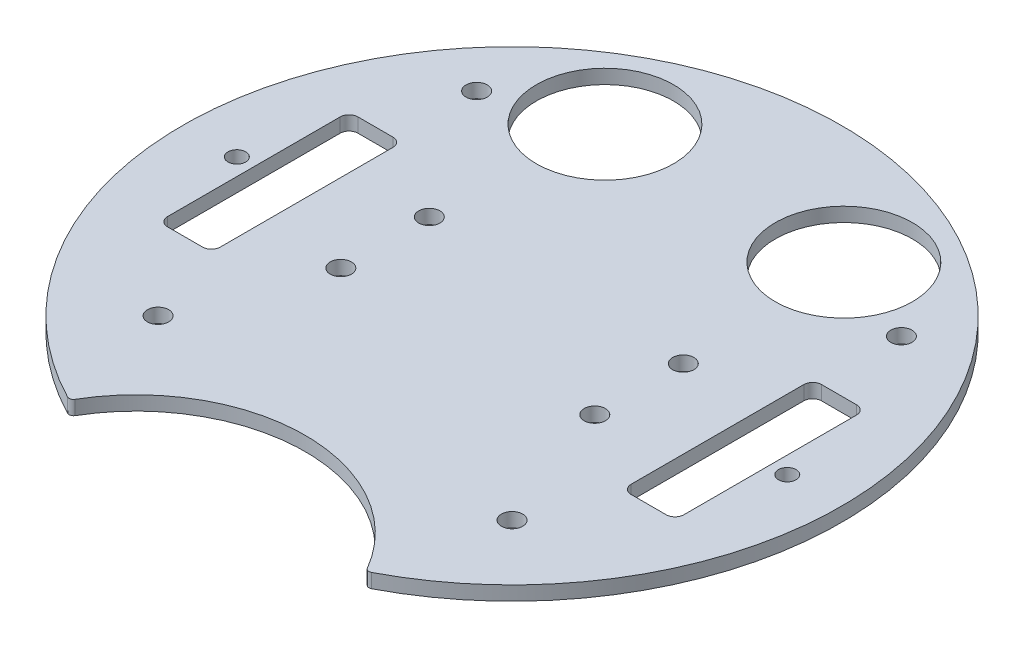
SolidWorks part; units mm, degrees
material "Plain Carbon Steel"
ref_plane "Front Plane" through (0, 0, 0) normal (0, 0, 1) x (1, 0, 0)
ref_plane "Top Plane" through (0, 0, 0) normal (0, 1, 0) x (1, 0, 0)
ref_plane "Right Plane" through (0, 0, 0) normal (1, 0, 0) x (0, 0, -1)
sketch "Sketch1" plane through (0, 0, 0) normal (0, 1, 0) x (1, 0, 0)
  line L1 (0, -85) -> (0, 0) construction
  arc A0 (34.3603, -66.1031) -> (-34.3603, -66.1031) centre (0, 0) ccw
  arc A1 (33.0354, -65.7199) -> (-33.0354, -65.7199) centre (0, -85) ccw
  arc A2 (34.3603, -66.1031) -> (33.0354, -65.7199) centre (33.8991, -65.2158) cw
  arc A3 (-33.0354, -65.7199) -> (-34.3603, -66.1031) centre (-33.8991, -65.2158) cw
  dimension "D1" = 149
  dimension "D2" = 76.5
  dimension "D4" = 1
  dimension "D3" = 85
extrude "Boss-Extrude1" add sketch "Sketch1" along normal blind 3.2
sketch "solenoid placement" plane through (0, 3.2, 0) normal (0, 1, 0) x (1, 0, 0)
  line L0 (0, 0) -> (0, -36) construction
  line L1 (0, -36) -> (0, -46.75) construction
  line L2 (-19, -36) -> (19, -36)
  line L3 (-19, -36) -> (-19, 28)
  line L4 (-19, 28) -> (19, 28)
  line L5 (19, -36) -> (19, 28)
  circle A1 centre (0, 0) radius 74.5 construction
  arc A2 (34.3603, -66.1031) -> (-34.3603, -66.1031) centre (0, 0) ccw construction
  arc A3 (33.0354, -65.7199) -> (-33.0354, -65.7199) centre (0, -85) ccw construction
  dimension "D1" = 64
  dimension "D2" = 36
  dimension "D4" = 38
sketch "Sketch2" plane through (0, 3.2, 0) normal (0, 1, 0) x (1, 0, 0)
  line L1 (-57.47, 20.6344) -> (-47.31, 20.6344) construction
  line L2 (-57.47, 20.6344) -> (-57.47, -20.6344) construction
  line L3 (-57.47, -20.6344) -> (-47.31, -20.6344) construction
  line L4 (-47.31, 20.6344) -> (-47.31, -20.6344) construction
  line L8 (-57.77, -20.9344) -> (-47.01, -20.9344)
  line L9 (-47.01, 20.9344) -> (-47.01, -20.9344)
  line L10 (-57.77, 20.9344) -> (-47.01, 20.9344)
  line L11 (-57.77, 20.9344) -> (-57.77, -20.9344)
  line L12 (0, 0) -> (0, 74.5) construction
  line L13 (47.31, 20.6344) -> (47.31, -20.6344) construction
  line L14 (57.47, -20.6344) -> (47.31, -20.6344) construction
  line L15 (57.47, 20.6344) -> (57.47, -20.6344) construction
  line L16 (57.47, 20.6344) -> (47.31, 20.6344) construction
  line L17 (57.77, 20.9344) -> (57.77, -20.9344)
  line L18 (57.77, 20.9344) -> (47.01, 20.9344)
  line L19 (47.01, 20.9344) -> (47.01, -20.9344)
  line L20 (57.77, -20.9344) -> (47.01, -20.9344)
  arc A0 (34.3603, -66.1031) -> (-34.3603, -66.1031) centre (0, 0) ccw construction
extrude "Cut-Extrude1" cut sketch "Sketch2" against normal through all
sketch "Sketch3" plane through (0, 0, 0) normal (0, -1, 0) x (1, 0, 0)
  line L0 (0, 0) -> (0, -74.5) construction
  circle A0 centre (-62.2, 0) radius 2
  circle A1 centre (-28.7007, 10) radius 2.4
  circle A2 centre (-28.7007, -10) radius 2.4
  arc A3 (-34.3603, 66.1031) -> (34.3603, 66.1031) centre (0, 0) ccw construction
  circle A4 centre (28.7007, -10) radius 2.4
  circle A5 centre (28.7007, 10) radius 2.4
  circle A6 centre (62.2, 0) radius 2
  dimension "D1" = 4
  dimension "D2" = 4.8
extrude "Cut-Extrude2" cut sketch "Sketch3" against normal through all
sketch "Sketch4" plane through (0, 3.2, 0) normal (0, 1, 0) x (1, 0, 0)
  line L0 (0, 0) -> (0, 74.5) construction
  line L1 (0, 48) -> (-27, 48) construction
  circle A0 centre (-27, 48) radius 15
  arc A1 (34.3603, -66.1031) -> (-34.3603, -66.1031) centre (0, 0) ccw construction
  circle A2 centre (27, 48) radius 15
  dimension "D1" = 30
  dimension "D2" = 48
  dimension "D3" = 27
extrude "Cut-Extrude3" cut sketch "Sketch4" against normal through all
sketch "Sketch5" plane through (0, 3.2, 0) normal (0, 1, 0) x (1, 0, 0)
  line L0 (0, 0) -> (0, 74.5) construction
  line L1 (-56.3558, 21.5201) -> (-48.4242, 21.5201)
  line L2 (-58.3558, 19.5201) -> (-58.3558, -19.5201)
  line L3 (-56.3558, -21.5201) -> (-48.4242, -21.5201)
  line L4 (-46.4242, 19.5201) -> (-46.4242, -19.5201)
  line L5 (46.4242, 19.5201) -> (46.4242, -19.5201)
  line L6 (56.3558, -21.5201) -> (48.4242, -21.5201)
  line L7 (58.3558, 19.5201) -> (58.3558, -19.5201)
  line L8 (56.3558, 21.5201) -> (48.4242, 21.5201)
  arc A0 (-58.3558, -19.5201) -> (-56.3558, -21.5201) centre (-56.3558, -19.5201) ccw
  arc A1 (-48.4242, -21.5201) -> (-46.4242, -19.5201) centre (-48.4242, -19.5201) ccw
  arc A2 (-48.4242, 21.5201) -> (-46.4242, 19.5201) centre (-48.4242, 19.5201) cw
  arc A3 (-56.3558, 21.5201) -> (-58.3558, 19.5201) centre (-56.3558, 19.5201) ccw
  arc A4 (34.3603, -66.1031) -> (-34.3603, -66.1031) centre (0, 0) ccw construction
  arc A5 (56.3558, 21.5201) -> (58.3558, 19.5201) centre (56.3558, 19.5201) cw
  arc A6 (48.4242, 21.5201) -> (46.4242, 19.5201) centre (48.4242, 19.5201) ccw
  arc A7 (48.4242, -21.5201) -> (46.4242, -19.5201) centre (48.4242, -19.5201) cw
  arc A8 (58.3558, -19.5201) -> (56.3558, -21.5201) centre (56.3558, -19.5201) cw
  point P15 (-57.77, 20.9344)
  dimension "D1" = 2
extrude "Cut-Extrude4" cut sketch "Sketch5" against normal through all
sketch "Sketch6" plane through (0, 3.2, 0) normal (0, 1, 0) x (1, 0, 0)
  line L0 (0, 74.5) -> (0, -46.75) construction
  circle A0 centre (48, 40) radius 2.4
  circle A1 centre (-40, -40) radius 2.4
  arc A4 (34.3603, -66.1031) -> (-34.3603, -66.1031) centre (0, 0) ccw construction
  arc A5 (33.0354, -65.7199) -> (-33.0354, -65.7199) centre (0, -85) ccw construction
  circle A6 centre (40, -40) radius 2.4
  circle A7 centre (-48, 40) radius 2.4
  dimension "D3" = 4.8
  dimension "D1" = 40
  dimension "D2" = 40
  dimension "D4" = 48
  dimension "D5" = 40
extrude "Cut-Extrude5" cut sketch "Sketch6" against normal through all
chamfer "Chamfer1" [suppressed] distance 2 angle 41
sketch "Sketch8" plane through (0, 3.2, 0) normal (0, 1, 0) x (1, 0, 0)
  circle A0 centre (-27, 48) radius 15.5
  circle A1 centre (27, 48) radius 15.5
  dimension "D1" = 31
extrude "Cut-Extrude6" cut sketch "Sketch8" against normal through all
equation "\"smallPulleyTeeth\"= 30"
equation "\"largePulleyTeeth\"= 30"
equation "\"eighthThick\"= 3.0mm"
equation "\"sixteenthThick\" = 1.7mm"
equation "\"quarterThick\"=6.0mm"
equation "\"OD\" = 145mm"
equation "\"puckAngle\" = 60.5deg"
equation "\"puckDiam\" = 76.5mm"
equation "\"D2@Sketch1\"=\"puckDiam\""
equation "\"D1@Boss-Extrude1\"=\"eighthThick\""
equation "\"axlePress\" = 5.9mm"
equation "\"press\" = 0.2mm"
equation "\"wheelClear\" = 0.3mm"
equation "\"D1@Sketch2\"=\"wheelClear\""
equation "\"10-32clear\" = 4.8mm"
equation "\"6-32clear\" = 3.3mm"
equation "\"8-32clear\" = 4.0mm"
equation "\"wheelHeight\" = 22mm"
equation "\"D1@Sketch3\"=\"8-32clear\""
equation "\"D2@Sketch3\"=\"10-32clear\""
equation "\"D3@Sketch6\"=\"10-32clear\""
equation "\"puckDist\" = 85mm"
equation "\"4-40clear\" = 3.0mm"
equation "\"wheelWell\" = 65mm"
equation "\"D3@Sketch1\"=\"puckDist\""
